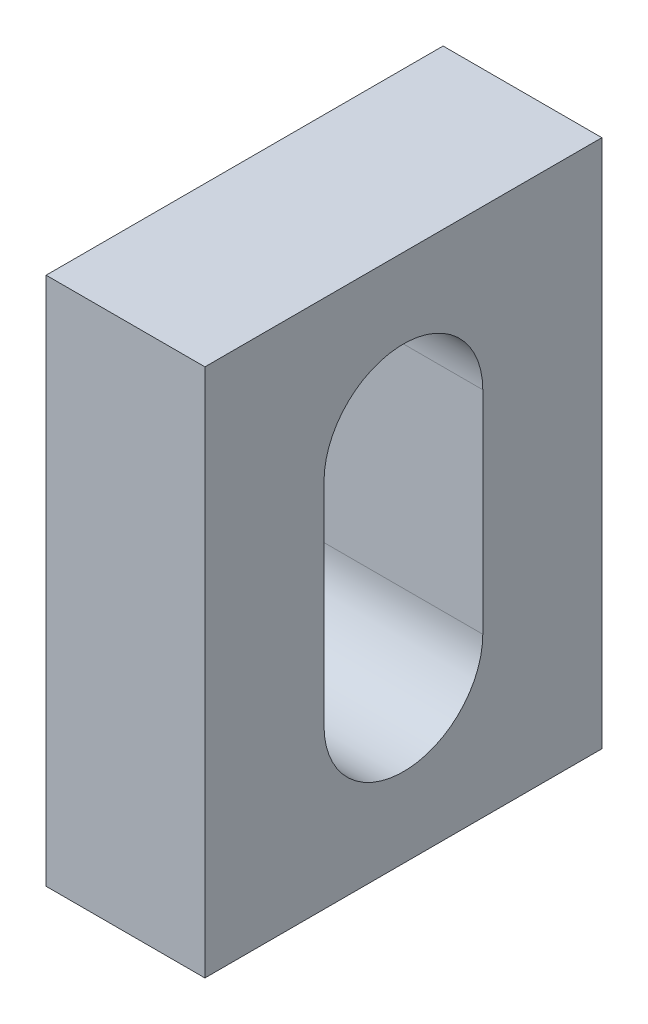
SolidWorks part; units mm, degrees
material "Acrilico TEC"
ref_plane "Front Plane" through (0, 0, 0) normal (0, 0, 1) x (1, 0, 0)
ref_plane "Top Plane" through (0, 0, 0) normal (0, 1, 0) x (1, 0, 0)
ref_plane "Right Plane" through (0, 0, 0) normal (1, 0, 0) x (0, 0, -1)
sketch "Sketch1" plane through (0, 0, 0) normal (1, 0, 0) x (0, 0, -1)
  line L0 (7.5, 6) -> (7.5, 14) construction
  line L1 (0, 0) -> (15, 0)
  line L2 (0, 0) -> (0, 20)
  line L3 (0, 20) -> (15, 20)
  line L4 (15, 0) -> (15, 20)
  line L5 (4.5, 6) -> (4.5, 14)
  line L6 (10.5, 6) -> (10.5, 14)
  arc A0 (4.5, 6) -> (10.5, 6) centre (7.5, 6) ccw
  arc A1 (10.5, 14) -> (4.5, 14) centre (7.5, 14) ccw
  point P8 (7.5, 10)
  dimension "D4" = 3
  dimension "D1" = 15
  dimension "D2" = 20
  dimension "D3" = 6
  dimension "D5" = 8
  dimension "D6" = 7.5
extrude "Boss-Extrude1" add sketch "Sketch1" along normal blind 6
